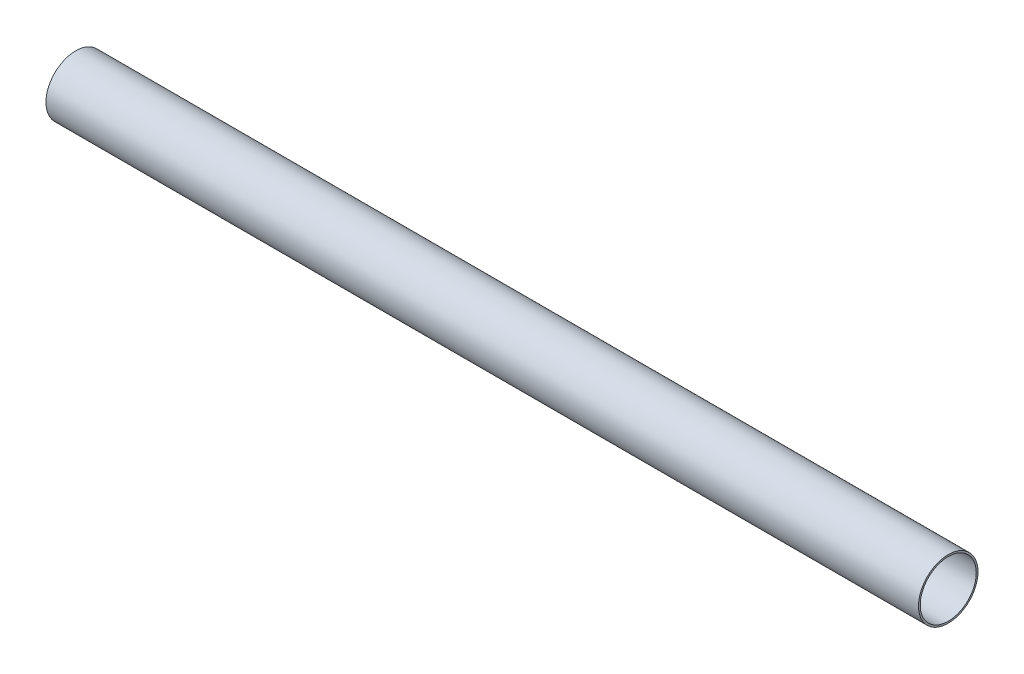
SolidWorks part; units mm, degrees
ref_plane "Front Plane" through (0, 0, 0) normal (1, 0, 0) x (0, 1, 0)
ref_plane "Top Plane" through (0, 0, 0) normal (0, 0, 1) x (0, 1, 0)
ref_plane "Right Plane" through (0, 0, 0) normal (0, 1, 0) x (-1, 0, 0)
sketch "Sketch1" plane through (0, 0, 0) normal (1, 0, 0) x (0, 1, 0)
  circle A0 centre (0, 0) radius 170.5
  dimension "D1" = 341
extrude "Boss-Extrude1" add sketch "Sketch1" along normal blind 2500 and the other way blind 2500
shell "Shell1" thickness 10 removed face at (-2500, 0, -170.5) removed face at (2500, 0, -170.5)
